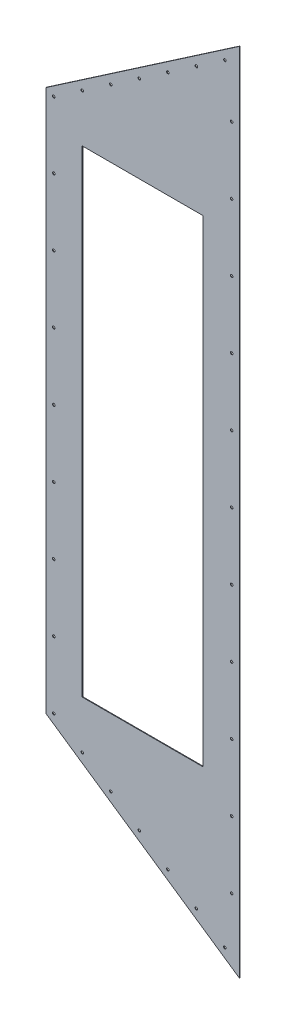
SolidWorks part; units mm, degrees
note: '?' marks a value the reader was unsure of.
ref_plane "Alzado" through (0, 0, 0) normal (0, 0, 1) x (1, 0, 0)
ref_plane "Planta" through (0, 0, 0) normal (0, 1, 0) x (1, 0, 0)
ref_plane "Vista lateral" through (0, 0, 0) normal (1, 0, 0) x (0, 0, -1)
sketch "Croquis1" plane through (0, 0, 0) normal (0, 0, 1) x (1, 0, 0)
  line L0 (-251.585, -706) -> (251.585, -1050.4)
  line L1 (-251.585, -706) -> (251.585, -706) construction
  line L2 (-251.585, -706) -> (-251.585, 706)
  line L3 (-251.585, 706) -> (251.585, 706) construction
  line L4 (251.585, -706) -> (251.585, 706)
  line L5 (-251.585, -706) -> (251.585, 706) construction
  line L6 (-251.585, 706) -> (251.585, -706) construction
  line L7 (251.585, -1050.4) -> (251.585, -706)
  line L10 (-251.585, 706) -> (251.585, 1050.4)
  line L11 (251.585, 1050.4) -> (251.585, 706)
  point P0 (0, 0)
  dimension "D1" = 1412
  dimension "D2" = 503.17
  dimension "D3" = 344.4
  dimension "D4" = 344.4
base flange "Brida base1" sketch "Croquis1" thickness 1.5875 reverse thickness direction no parameters "D1"=0.7366
sketch "Croquis4" plane through (0, 0, 0) normal (0, 0, 1) x (1, 0, 0)
  line L0 (-251.585, 681.7638) -> (251.585, 1026.1638) construction
  line L1 (-251.585, 706) -> (-251.585, -706) construction
  line L2 (251.585, -1050.4) -> (251.585, 1050.4) construction
  line L3 (251.585, 1050.4) -> (-251.585, 706) construction
  dimension "D1" = 20
ref_axis "Eje1" through (-251.585, 681.7638, 0) along (0.8252, 0.5648, 0)?
hole_wizard "Taladro de margen para M61" positions "Croquis6" profile "Croquis5" hole size "M6" standard "Ansi Metric" end condition through all
sketch "Croquis6" plane through (0, 0, 0) normal (0, 0, 1) x (1, 0, 0)
  line L0 (-251.585, 681.7638) -> (251.585, 1026.1638) construction
  line L1 (-251.585, 0) -> (251.585, 0) construction
  line L2 (-251.585, 706) -> (-251.585, -706) construction
  line L3 (251.585, -1050.4) -> (251.585, 1050.4) construction
  line L4 (-251.585, 681.7638) -> (251.585, 1026.1638) construction
  line L6 (-251.585, -681.7638) -> (251.585, -1026.1638) construction
  line L7 (-231.585, 695.453) -> (-231.585, -695.453) construction
  line L8 (0, 0) -> (0, 647.5626) construction
  line L10 (231.585, 695.453) -> (231.585, -695.453) construction
  point P0 (-231.585, 695.453)
  point P13 (-157.3169, 746.2886)
  point P14 (-83.0489, 797.1241)
  point P15 (-8.7808, 847.9597)
  point P16 (65.4873, 898.7952)
  point P17 (139.7553, 949.6308)
  point P18 (214.0234, 1000.4664)
  point P32 (65.4873, -898.7952)
  point P33 (-8.7808, -847.9597)
  point P34 (-83.0489, -797.1241)
  point P35 (-157.3169, -746.2886)
  point P36 (-231.585, -695.453)
  point P37 (214.0234, -1000.4664)
  point P38 (139.7553, -949.6308)
  point P53 (-231.585, -521.453)
  point P54 (-231.585, -347.453)
  point P55 (-231.585, -173.453)
  point P56 (-231.585, 0.547)
  point P57 (-231.585, 174.547)
  point P58 (-231.585, 348.547)
  point P59 (-231.585, 522.547)
  point P67 (231.585, 522.547)
  point P68 (231.585, 348.547)
  point P69 (231.585, 174.547)
  point P70 (231.585, 0.547)
  point P71 (231.585, -173.453)
  point P72 (231.585, -347.453)
  point P73 (231.585, -521.453)
  point P78 (231.585, -695.453)
  point P79 (231.585, -869.453)
  point P86 (231.585, 696.547)
  point P87 (231.585, 870.547)
  dimension "D1" = 20
  dimension "D3" = 8
  dimension "D2" = 7
  dimension "D4" = 3
  dimension "D5" = 3
sketch "Croquis5" plane through (-231.585, 695.453, 0) normal (1, 0, 0) x (0, -1, 0)
  line L0 (0, 0) -> (0, 1.5875)
  line L1 (0, 1.5875) -> (3.3, 1.5875)
  line L2 (3.3, 1.5875) -> (3.3, 0)
  line L5 (3.3, 0) -> (0, 0)
  line L11 (0, -6.35) -> (0, 107.95) construction
  dimension "Diámetro de taladro hasta el siguiente" = 6.6
  dimension "Profundidad de taladro hasta el siguiente" = 1.5875
sketch "Croquis7" plane through (0, 0, -1.5875) normal (0, 0, 1) x (1, 0, 0)
  line L1 (157.4878, -621.4241) -> (-157.4878, -621.4241)
  line L2 (157.4878, -621.4241) -> (157.4878, 621.4241)
  line L3 (157.4878, 621.4241) -> (-157.4878, 621.4241)
  line L4 (-157.4878, -621.4241) -> (-157.4878, 621.4241)
  line L5 (157.4878, -621.4241) -> (-157.4878, 621.4241) construction
  line L6 (157.4878, 621.4241) -> (-157.4878, -621.4241) construction
  point P0 (0, 0)
extrude "Cortar-Extruir2" cut sketch "Croquis7" along normal blind 3200 normal cut yes
sketch "Líneas de pliegue1" [suppressed] plane through (0, 0, 0) normal (0, 1, 0) x (1, 0, 0)
sketch "Cuadro delimitador1" [suppressed] plane through (0, 0, 0) normal (0, 1, 0) x (1, 0, 0)
sheet metal parameters "Chapa metálica1" thickness 1.5875 parameters "D1"=0.7366
flat pattern "Chapa desplegada1" [suppressed]
sketch "Líneas de pliegue2" plane through (0, 0, 0) normal (0, 1, 0) x (1, 0, 0)
sketch3d "Cuadro delimitador2" [suppressed]
  line L0 (252.7, 1051.94, 0) -> (252.7, -1051.94, 0) construction
  line L1 (-252.7, 1051.94, 0) -> (-252.7, -1051.94, 0) construction
  line L2 (252.7, 1051.94, 0) -> (-252.7, 1051.94, 0) construction
  line L3 (252.7, -1051.94, 0) -> (-252.7, -1051.94, 0) construction
sheet metal parameters "Chapa metálica2" thickness 1.5875 parameters "D1"=0.7366
flat pattern "Chapa desplegada1" [suppressed]
sketch "Líneas de pliegue2" plane through (0, 0, 0) normal (0, 1, 0) x (1, 0, 0)
sketch3d "Cuadro delimitador2" [suppressed]
  line L0 (252.7, 1051.94, 0) -> (252.7, -1051.94, 0) construction
  line L1 (-252.7, 1051.94, 0) -> (-252.7, -1051.94, 0) construction
  line L2 (252.7, 1051.94, 0) -> (-252.7, 1051.94, 0) construction
  line L3 (252.7, -1051.94, 0) -> (-252.7, -1051.94, 0) construction
sketch "Croquis7-1" [suppressed] plane through (0, 0, -1.5875) normal (0, 0, 1) x (1, 0, 0)
  line L1 (157.4878, -621.4241) -> (-157.4878, -621.4241)
  line L2 (157.4878, -621.4241) -> (157.4878, 621.4241)
  line L3 (157.4878, 621.4241) -> (-157.4878, 621.4241)
  line L4 (-157.4878, -621.4241) -> (-157.4878, 621.4241)
  line L5 (157.4878, -621.4241) -> (-157.4878, 621.4241) construction
  line L6 (157.4878, 621.4241) -> (-157.4878, -621.4241) construction
  point P0 (0, 0)
sheet metal parameters "Chapa metálica5" thickness 1.5875 parameters "D1"=0.7366
flat pattern "Chapa desplegada1" [suppressed]
sketch "Líneas de pliegue2" plane through (0, 0, 0) normal (0, 1, 0) x (1, 0, 0)
sketch3d "Cuadro delimitador2" [suppressed]
  line L0 (251.585, 1050.4, 0) -> (251.585, -1050.4, 0) construction
  line L1 (-251.585, 1050.4, 0) -> (-251.585, -1050.4, 0) construction
  line L2 (251.585, 1050.4, 0) -> (-251.585, 1050.4, 0) construction
  line L3 (251.585, -1050.4, 0) -> (-251.585, -1050.4, 0) construction
sketch "Croquis7-1" plane through (0, 0, -1.5875) normal (0, 0, 1) x (1, 0, 0)
  line L1 (157.4878, -621.4241) -> (-157.4878, -621.4241)
  line L2 (157.4878, -621.4241) -> (157.4878, 621.4241)
  line L3 (157.4878, 621.4241) -> (-157.4878, 621.4241)
  line L4 (-157.4878, -621.4241) -> (-157.4878, 621.4241)
  line L5 (157.4878, -621.4241) -> (-157.4878, 621.4241) construction
  line L6 (157.4878, 621.4241) -> (-157.4878, -621.4241) construction
  point P0 (0, 0)
sketch "Croquis7-2" [suppressed] plane through (0, 0, -1.5875) normal (0, 0, 1) x (1, 0, 0)
  line L1 (157.4878, -621.4241) -> (-157.4878, -621.4241)
  line L2 (157.4878, -621.4241) -> (157.4878, 621.4241)
  line L3 (157.4878, 621.4241) -> (-157.4878, 621.4241)
  line L4 (-157.4878, -621.4241) -> (-157.4878, 621.4241)
  line L5 (157.4878, -621.4241) -> (-157.4878, 621.4241) construction
  line L6 (157.4878, 621.4241) -> (-157.4878, -621.4241) construction
  point P0 (0, 0)
sketch "Croquis7-3" plane through (0, 0, -1.5875) normal (0, 0, 1) x (1, 0, 0)
  line L1 (157.4878, -621.4241) -> (-157.4878, -621.4241)
  line L2 (157.4878, -621.4241) -> (157.4878, 621.4241)
  line L3 (157.4878, 621.4241) -> (-157.4878, 621.4241)
  line L4 (-157.4878, -621.4241) -> (-157.4878, 621.4241)
  line L5 (157.4878, -621.4241) -> (-157.4878, 621.4241) construction
  line L6 (157.4878, 621.4241) -> (-157.4878, -621.4241) construction
  point P0 (0, 0)
sketch "Croquis7-4" plane through (0, 0, -1.5875) normal (0, 0, 1) x (1, 0, 0)
  line L1 (157.4878, -621.4241) -> (-157.4878, -621.4241)
  line L2 (157.4878, -621.4241) -> (157.4878, 621.4241)
  line L3 (157.4878, 621.4241) -> (-157.4878, 621.4241)
  line L4 (-157.4878, -621.4241) -> (-157.4878, 621.4241)
  line L5 (157.4878, -621.4241) -> (-157.4878, 621.4241) construction
  line L6 (157.4878, 621.4241) -> (-157.4878, -621.4241) construction
  point P0 (0, 0)
